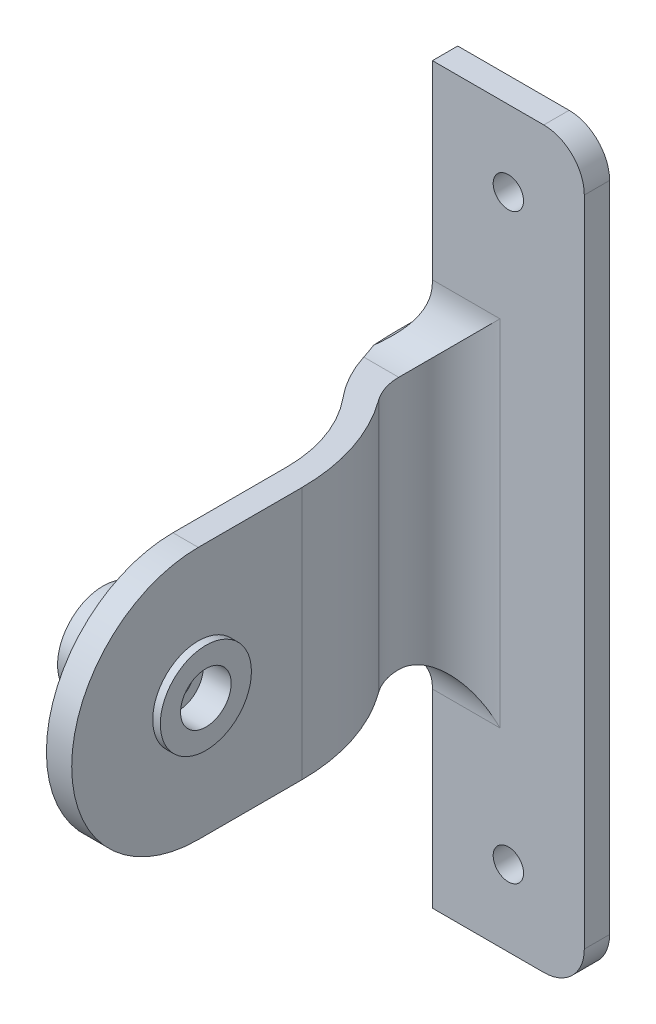
SolidWorks part; units mm, degrees
ref_plane "Front Plane" through (0, 0, 0) normal (0, 0, 1) x (1, 0, 0)
ref_plane "Top Plane" through (0, 0, 0) normal (0, 1, 0) x (1, 0, 0)
ref_plane "Right Plane" through (0, 0, 0) normal (1, 0, 0) x (0, 0, -1)
sketch "Sketch1" plane through (0, 0, 0) normal (1, 0, 0) x (0, 0, -1)
  line L1 (0, 12.5) -> (34.45, 12.5)
  line L2 (0, 1.5) -> (0, -12.5)
  line L3 (0, -12.5) -> (34.45, -12.5)
  line L4 (34.45, 12.5) -> (34.45, -12.5)
  circle A0 centre (0, 0) radius 1.5
  circle A1 centre (0, 0) radius 12.5 construction
  arc A2 (0, 12.5) -> (0, -12.5) centre (0, 0) ccw
  dimension "D1" = 3
  dimension "D2" = 25
  dimension "D3" = 34.45
extrude "Boss-Extrude1" add sketch "Sketch1" along normal blind 2.5 contours L1 A2 A0 L3 L4 region at (0, 0, -12.3069)
sketch "Sketch2" plane through (0, 0, 0) normal (-1, 0, 0) x (0, 0, 1)
  circle A0 centre (0, 0) radius 1.5
  circle A1 centre (0, 0) radius 4.5
  dimension "D1" = 9
  dimension "D2" = 3
extrude "Boss-Extrude2" add sketch "Sketch2" along normal blind 6.9 and the other way offset from surface 0.75 other way up to face at (2.5, 0, -14.1)
sketch "Sketch4" plane through (2.5, 0, 0) normal (1, 0, 0) x (0, 0, -1)
  circle A0 centre (0, 0) radius 2.5
extrude "Cut-Extrude1" cut sketch "Sketch4" against normal blind 2
sketch "Sketch5" plane through (2.5, 0, 0) normal (1, 0, 0) x (0, 0, -1)
  circle A0 centre (0, 0) radius 4.5
  circle A1 centre (0, 0) radius 2.5
  dimension "D1" = 9
  dimension "D2" = 5
extrude "Boss-Extrude3" add sketch "Sketch5" along normal blind 0.75
sketch "Sketch6" plane through (0, 0, -34.45) normal (0, 0, -1) x (-1, 0, 0)
  line L1 (-8.8125, 36.25) -> (53.3216, 36.25)
  line L3 (6.25, -36.25) -> (53.3216, -36.25)
  line L4 (53.3216, 36.25) -> (53.3216, -36.25)
  line L6 (53.3216, -36.25) -> (-19.1784, 36.25) construction
  line L7 (6.25, -36.25) -> (-19.1784, -36.25)
  line L9 (-8.8125, 36.25) -> (-19.1784, 36.25)
  line L10 (-19.1784, -36.25) -> (-19.1784, 36.25)
  line L11 (53.3216, 36.25) -> (-19.1784, -36.25) construction
  point P4 (17.0716, 0)
  dimension "D1" = 72.5
  dimension "D2" = 72.5
extrude "Boss-Extrude4" add sketch "Sketch6" against normal blind 2.5
ref_plane "Plane1" through (-17.0716, 0, 0) normal (1, 0, 0) x (0, 0, -1)
ref_plane "Plane2" through (9.4784, 0, 0) normal (1, 0, 0) x (0, 0, -1)
sketch "Sketch7" plane through (0, 0, -31.95) normal (0, 0, 1) x (1, 0, 0)
  line L7 (1.7881, -3.3824) -> (-5.2119, -3.3824)
  line L12 (1.7881, -3.3824) -> (1.7881, -19.8824)
  line L18 (1.7881, -19.8824) -> (-5.2119, -19.8824)
  line L19 (-5.2119, -3.3824) -> (-5.2119, -19.8824)
  line L20 (1.7881, -3.3824) -> (-5.2119, -19.8824) construction
  line L21 (1.7881, -19.8824) -> (-5.2119, -3.3824) construction
  line L22 (-24.5, -4) -> (-8.5, -4)
  line L23 (-24.5, -4) -> (-24.5, 4)
  line L24 (-24.5, 4) -> (-8.5, 4)
  line L25 (-8.5, -4) -> (-8.5, 4)
  line L26 (-24.5, -4) -> (-8.5, 4) construction
  line L27 (-24.5, 4) -> (-8.5, -4) construction
  point P0 (-16.5, 0)
  point P2 (-1.7119, -11.6324)
  dimension "D1" = 16
  dimension "D2" = 16.5
  dimension "D3" = 7
  dimension "D4" = 8
extrude "Cut-Extrude2" cut sketch "Sketch7" against normal up to next
sketch "Sketch8" plane through (0, 0, 0) normal (0, 1, 0) x (1, 0, 0)
  line L13 (0, 7.7296) -> (2.5, 7.7296)
  line L17 (0, 11.2296) -> (0, 7.7296)
  line L18 (-3.7212, 31.95) -> (-3.7212, 29.45)
  line L19 (-6.2212, 31.95) -> (-6.2212, 28.45)
  line L20 (-6.2212, 31.95) -> (-3.7212, 31.95)
  line L22 (2.5, 7.7296) -> (2.5, 10.2296)
  line L23 (2.5, 0) -> (2.5, 31.95) construction
  line L24 (0, 0) -> (0, 31.95) construction
  line L25 (0, -13.75) -> (0, 13.75) construction
  line L26 (-53.3216, 31.95) -> (19.1784, 31.95) construction
  line L27 (19.1784, 31.95) -> (19.1784, 34.45) construction
  arc A5 (-1.1155, 21.3996) -> (2.5, 10.2296) centre (-16.5626, 10.2296) cw
  arc A6 (-3.1485, 19.9446) -> (-6.2212, 28.45) centre (7.0867, 28.45) cw
  arc A7 (-3.1485, 19.9446) -> (0, 11.2296) centre (-13.636, 11.2296) cw
  arc A8 (-3.7212, 29.45) -> (-1.1155, 21.3996) centre (10.0176, 29.45) ccw
  dimension "D3" = 22.8996
  dimension "D4" = 3.5
  dimension "D1" = 2.5
  dimension "D2" = 2.5
  dimension "D5" = 3.5
  dimension "D6" = 2.5
  dimension "D7" = 2.5
sketch "Sketch9" plane through (0, -12.5, 0) normal (0, -1, 0) x (1, 0, 0)
  line L0 (2.5, 0) -> (2.5, -31.95) construction
  line L1 (0, -31.95) -> (2.5, -31.95)
  line L2 (0, -31.95) -> (0, -9.5612)
  line L3 (0, -9.5612) -> (2.5, -9.5612)
  line L4 (2.5, -31.95) -> (2.5, -9.5612)
extrude "Cut-Extrude3" cut sketch "Sketch9" against normal up to next
extrude "Boss-Extrude5" add sketch "Sketch8" along normal mid plane 25
fillet "Fillet1" [suppressed] radius 4
fillet "Fillet2" radius 1 8 edges at (-5.2119, -3.3824, -33.2) (-5.2119, -19.8824, -33.2) (1.7881, -3.3824, -33.2) (-8.5, 4, -33.2) (1.7881, -19.8824, -33.2) (-8.5, -4, -33.2) (-24.5, 4, -33.2) (-24.5, -4, -33.2)
fillet "Fillet3" radius 4 4 edges at (19.1784, -36.25, -33.2) (19.1784, 36.25, -33.2) (-53.3216, 36.25, -33.2) (-53.3216, -36.25, -33.2)
sketch "Sketch10" plane through (0, 0, 0) normal (0, 1, 0) x (1, 0, 0)
  line L0 (15.1784, 31.95) -> (19.1784, 31.95) construction
  line L1 (21.7259, 31.95) -> (-56.5098, 31.95)
  line L2 (21.7259, 31.95) -> (21.7259, 38.24)
  line L3 (21.7259, 38.24) -> (-56.5098, 38.24)
  line L4 (-56.5098, 31.95) -> (-56.5098, 38.24)
extrude "Cut-Extrude4" cut sketch "Sketch10" against normal through all both and the other way through all
sketch "Sketch11" plane through (0, 0, 0) normal (0, 1, 0) x (1, 0, 0)
  line L0 (-3.7212, 29.45) -> (-3.7212, 31.95) construction
  line L1 (11.1788, 31.95) -> (-3.7212, 31.95)
  line L2 (11.1788, 31.95) -> (11.1788, 29.45)
  line L3 (11.1788, 29.45) -> (-3.7212, 29.45)
  line L4 (-3.7212, 31.95) -> (-3.7212, 29.45)
  line L5 (-3.7212, 31.95) -> (-6.2212, 31.95) construction
  dimension "D1" = 2.5
  dimension "D2" = 14.9
extrude "Boss-Extrude6" add sketch "Sketch11" along normal mid plane 25
sketch "Sketch12" plane through (0, 0, -31.95) normal (0, 0, -1) x (-1, 0, 0)
  line L0 (24.4475, 0) -> (-24.4475, 0) construction
  line L1 (-11.1788, 36.25) -> (61.3212, 36.25) construction
  line L2 (-11.1788, 36.25) -> (-11.1788, -36.25) construction
  line L3 (-11.1788, -36.25) -> (61.3212, -36.25) construction
  line L4 (61.3212, 36.25) -> (61.3212, -36.25) construction
  line L5 (-11.1788, 36.25) -> (61.3212, -36.25) construction
  line L6 (61.3212, 36.25) -> (-11.1788, -36.25) construction
  line L7 (-11.1788, 12.5) -> (-11.1788, -12.5) construction
  circle A0 centre (-3.6788, 28.75) radius 1.5
  circle A1 centre (-3.6788, -28.75) radius 1.5
  circle A2 centre (-3.6788, 28.75) radius 3
  circle A3 centre (-3.6788, -28.75) radius 3
  point P4 (-11.1788, 0)
  dimension "D3" = 3
  dimension "D5" = 6
  dimension "D1" = 72.5
  dimension "D2" = 72.5
  dimension "D4" = 7.5
sketch "Sketch13" plane through (0, 0, -31.95) normal (0, 0, -1) x (-1, 0, 0)
  line L1 (-11.1788, 12.5) -> (3.8212, 12.5)
  line L2 (-11.1788, 12.5) -> (-11.1788, 28.75)
  line L4 (3.8212, 12.5) -> (3.8212, 28.75)
  line L5 (-3.6788, 36.25) -> (-7.1788, 36.25)
  line L6 (-11.1788, 32.25) -> (-11.1788, 28.75)
  line L7 (3.8212, 28.75) -> (3.8212, 36.25)
  line L8 (3.8212, 36.25) -> (-3.6788, 36.25)
  arc A1 (-7.1788, 36.25) -> (-11.1788, 32.25) centre (-7.1788, 32.25) ccw
  dimension "D2" = 4
  dimension "D1" = 7.5
extrude "Boss-Extrude7" add sketch "Sketch13" against normal blind 2.5
mirror "Mirror1" about plane through (0, 0, 0) normal (0, 1, 0) of "Boss-Extrude6", "Boss-Extrude7"
sketch "Sketch14" plane through (0, 0, -31.95) normal (0, 0, -1) x (-1, 0, 0)
  line L0 (3.8212, 36.25) -> (-7.1788, 36.25) construction
  line L1 (3.8212, 12.5) -> (3.8212, 36.25) construction
  circle A0 centre (-3.6788, 28.75) radius 1.5
  dimension "D1" = 7.5
  dimension "D2" = 7.5
extrude "Cut-Extrude5" cut sketch "Sketch14" against normal blind 2.5
sketch "Sketch15" plane through (0, 0, -31.95) normal (0, 0, -1) x (-1, 0, 0)
  circle A0 centre (-3.6788, 28.75) radius 2.5
  circle A1 centre (-3.6788, 28.75) radius 4
  dimension "D1" = 8
  dimension "D2" = 5
extrude "Boss-Extrude8" [suppressed] add sketch "Sketch15" against normal blind 6
mirror "Mirror2" about plane through (0, 0, 0) normal (0, 1, 0) of "Cut-Extrude5", "Boss-Extrude8"
fillet "Fillet4" radius 5 3 edges at (-3.8212, -12.5, -30.7) (-3.8212, 12.5, -30.7) (-3.7212, 0, -29.45)
fillet "Fillet5" radius 5 2 edges at (-1.6853, -12.5, -29.45) (-1.6853, 12.5, -29.45)
